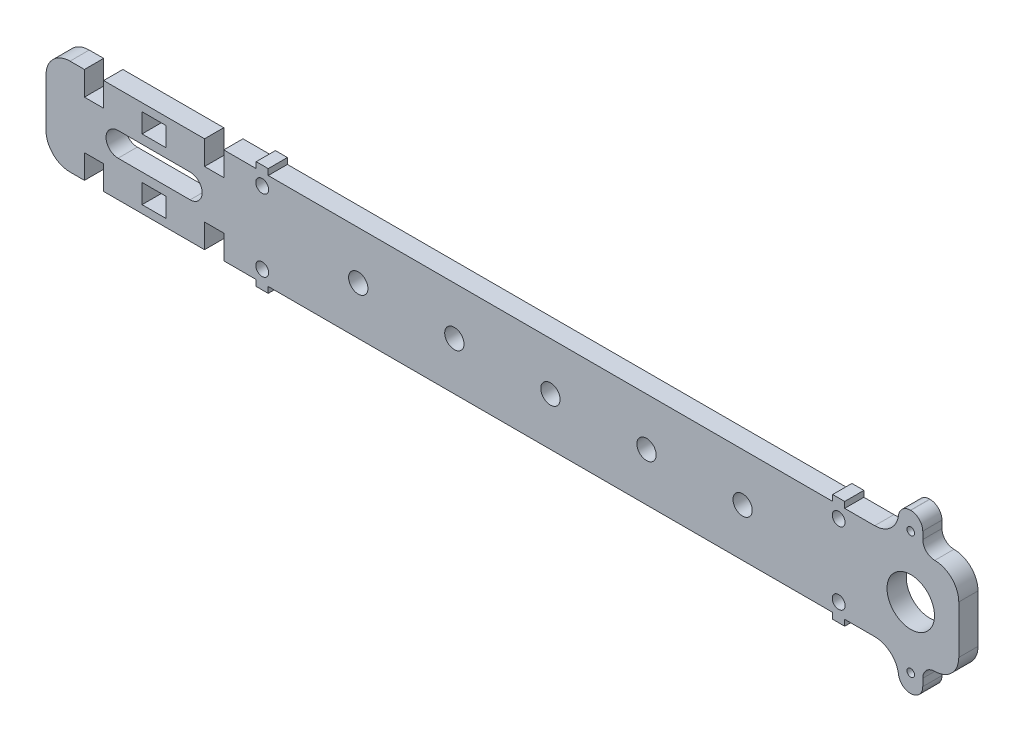
SolidWorks part; units mm, degrees
ref_plane "Front Plane" through (0, 0, 0) normal (0, 0, 1) x (1, 0, 0)
ref_plane "Top Plane" through (0, 0, 0) normal (0, 1, 0) x (1, 0, 0)
ref_plane "Right Plane" through (0, 0, 0) normal (1, 0, 0) x (0, 0, -1)
sketch "Sketch2" plane through (0, 0, 0) normal (0, 0, 1) x (1, 0, 0)
  line L0 (-120.65, 12.7) -> (-120.65, -12.7)
  line L1 (-120.65, 12.7) -> (120.65, 12.7) construction
  line L2 (-120.65, -12.7) -> (120.65, -12.7) construction
  line L3 (120.65, 12.7) -> (120.65, -12.7)
  line L4 (-120.65, 0) -> (120.65, 0) construction
  line L5 (-101.6, 0) -> (-82.55, 0) construction
  line L6 (-101.6, 3.175) -> (-82.55, 3.175)
  line L7 (-101.6, -3.175) -> (-82.55, -3.175)
  line L8 (107.95, -16.215) -> (107.95, 0) construction
  line L9 (107.95, 0) -> (107.95, 16.215) construction
  line L10 (111.125, 20.9775) -> (104.775, 20.9775)
  line L11 (104.775, -20.9775) -> (111.125, -20.9775)
  line L12 (104.775, 20.9775) -> (104.775, 12.7)
  line L14 (111.125, 20.9775) -> (111.125, 12.7)
  line L16 (120.65, -12.7) -> (111.125, -12.7)
  line L17 (111.125, -12.7) -> (111.125, -20.9775)
  line L18 (104.775, -20.9775) -> (104.775, -12.7)
  line L19 (104.775, -12.7) -> (-120.65, -12.7) construction
  line L20 (-63.5, 9.525) -> (-63.5, -9.525) construction
  line L21 (-63.5, -9.525) -> (88.9, -9.525) construction
  line L22 (88.9, -9.525) -> (88.9, 9.525) construction
  line L23 (88.9, 9.525) -> (-63.5, 9.525) construction
  line L25 (111.125, 12.7) -> (120.65, 12.7)
  line L39 (-61.9125, 12.7) -> (-61.9125, 14.2875)
  line L40 (-61.9125, 14.2875) -> (-65.0875, 14.2875)
  line L41 (-65.0875, 14.2875) -> (-65.0875, 12.7)
  line L45 (87.3125, 12.7) -> (87.3125, 14.2875)
  line L46 (87.3125, 14.2875) -> (90.4875, 14.2875)
  line L47 (90.4875, 14.2875) -> (90.4875, 12.7)
  line L52 (90.4875, 12.7) -> (104.775, 12.7)
  line L53 (-61.9125, 12.7) -> (87.3125, 12.7)
  line L54 (-65.0875, -12.7) -> (-65.0875, -14.2875)
  line L55 (-65.0875, -14.2875) -> (-61.9125, -14.2875)
  line L56 (-61.9125, -14.2875) -> (-61.9125, -12.7)
  line L57 (90.4875, -12.7) -> (90.4875, -14.2875)
  line L58 (90.4875, -14.2875) -> (87.3125, -14.2875)
  line L59 (87.3125, -14.2875) -> (87.3125, -12.7)
  line L61 (-61.9125, -12.7) -> (87.3125, -12.7)
  line L62 (104.775, -12.7) -> (90.4875, -12.7)
  line L63 (-76.2, 12.7) -> (-76.2, -12.7) construction
  line L64 (-78.74, 6.35) -> (-73.66, 6.35)
  line L65 (-78.74, -6.35) -> (-73.66, -6.35)
  line L66 (-78.74, 6.35) -> (-78.74, 12.7)
  line L67 (-78.74, 12.7) -> (-105.41, 12.7)
  line L68 (-105.41, 12.7) -> (-105.41, 6.35)
  line L69 (-105.41, 6.35) -> (-110.49, 6.35)
  line L70 (-110.49, 6.35) -> (-110.49, 12.7)
  line L71 (-110.49, 12.7) -> (-120.65, 12.7)
  line L72 (-78.74, -6.35) -> (-78.74, -12.7)
  line L73 (-78.74, -12.7) -> (-105.41, -12.7)
  line L74 (-105.41, -12.7) -> (-105.41, -6.35)
  line L75 (-105.41, -6.35) -> (-110.49, -6.35)
  line L76 (-110.49, -6.35) -> (-110.49, -12.7)
  line L77 (-110.49, -12.7) -> (-120.65, -12.7)
  line L78 (-73.66, 6.35) -> (-73.66, 12.7)
  line L79 (-73.66, 12.7) -> (-65.0875, 12.7)
  line L80 (-73.66, -6.35) -> (-73.66, -12.7)
  line L81 (-73.66, -12.7) -> (-65.0875, -12.7)
  line L82 (-107.95, 12.7) -> (-107.95, -12.7) construction
  line L83 (-92.075, 5.5562) -> (-92.075, -5.5562) construction
  line L84 (-95.25, 10.6363) -> (-88.9, 10.6363)
  line L85 (-95.25, 10.6363) -> (-95.25, 5.5562)
  line L86 (-95.25, 5.5562) -> (-88.9, 5.5562)
  line L87 (-88.9, 10.6363) -> (-88.9, 5.5562)
  line L88 (-95.25, -5.5562) -> (-88.9, -5.5562)
  line L89 (-95.25, -5.5562) -> (-95.25, -10.6363)
  line L90 (-95.25, -10.6363) -> (-88.9, -10.6363)
  line L91 (-88.9, -5.5562) -> (-88.9, -10.6363)
  arc A0 (-101.6, 3.175) -> (-101.6, -3.175) centre (-101.6, 0) ccw
  arc A1 (-82.55, -3.175) -> (-82.55, 3.175) centre (-82.55, 0) ccw
  circle A2 centre (107.95, 0) radius 6.275
  circle A3 centre (107.95, -16.215) radius 1
  circle A4 centre (107.95, 16.215) radius 1
  circle A6 centre (12.7, 0) radius 2.5527
  circle A7 centre (38.1, 0) radius 2.5527
  circle A8 centre (-12.7, 0) radius 2.5527
  circle A9 centre (-38.1, 0) radius 2.5527
  circle A10 centre (-63.5, 9.525) radius 1.7
  circle A11 centre (-63.5, -9.525) radius 1.7
  circle A12 centre (88.9, 9.525) radius 1.7
  circle A13 centre (88.9, -9.525) radius 1.7
  circle A14 centre (63.5, 0) radius 2.5527
  point P6 (0, 0)
  point P10 (-92.075, 0)
  point P21 (107.95, 20.9775)
  point P24 (107.95, -20.9775)
  point P47 (88.9, 0)
  point P48 (88.9, 14.2875)
  point P49 (-63.5, 14.2875)
  point P75 (-76.2, 6.35)
  point P76 (-76.2, -6.35)
  point P90 (-107.95, 6.35)
  point P102 (-92.075, 0)
  dimension "D2" = 12.55
  dimension "D3" = 2
  dimension "D9" = 12.7
  dimension "D16" = 5.1054
  dimension "D20" = 3.4
  dimension "D1" = 6.35
  dimension "D4" = 32.43
  dimension "D5" = 25.4
  dimension "D6" = 152.4
  dimension "D7" = 19.05
  dimension "D8" = 19.05
  dimension "D10" = 4.7625
  dimension "D11" = 6.35
  dimension "D12" = 12.7
  dimension "D13" = 12.7
  dimension "D14" = 25.4
  dimension "D15" = 25.4
  dimension "D17" = 19.05
  dimension "D18" = 19.05
  dimension "D19" = 3.175
  dimension "D21" = 3.175
  dimension "D22" = 6.35
  dimension "D23" = 1.5875
  dimension "D24" = 5.08
  dimension "D25" = 6.35
  dimension "D26" = 6.35
  dimension "D27" = 11.1125
  dimension "D28" = 25.4
  dimension "D29" = 26.67
extrude "Boss-Extrude1" add sketch "Sketch2" along normal blind 5.08
fillet "Fillet1" radius 6.35 6 edges at (120.65, -12.7, 2.54) (120.65, 12.7, 2.54) (104.775, 12.7, 2.54) (-120.65, 12.7, 2.54) (-120.65, -12.7, 2.54) (104.775, -12.7, 2.54)
fillet "Fillet2" radius 3.175 6 edges at (104.775, -20.9775, 2.54) (111.125, -20.9775, 2.54) (111.125, -12.7, 2.54) (111.125, 12.7, 2.54) (111.125, 20.9775, 2.54) (104.775, 20.9775, 2.54)
